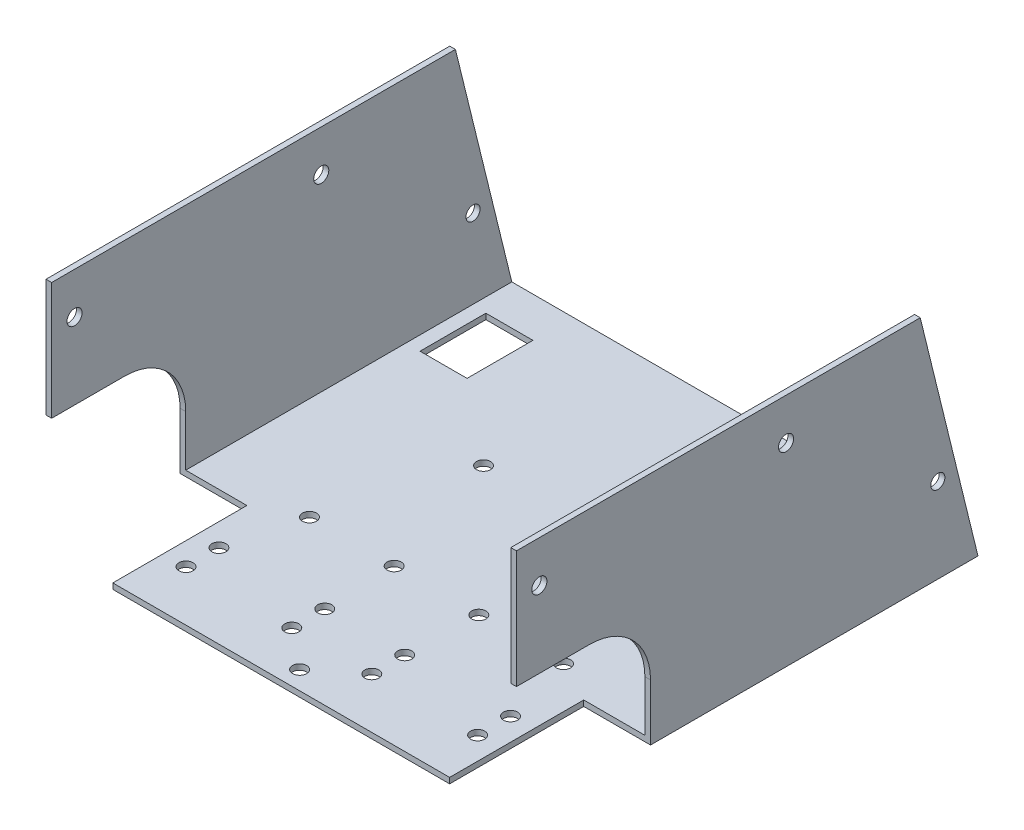
SolidWorks part; units mm, degrees
ref_plane "Alzado" through (0, 0, 0) normal (0, 0, 1) x (1, 0, 0)
ref_plane "Planta" through (0, 0, 0) normal (0, 1, 0) x (1, 0, 0)
ref_plane "Vista lateral" through (0, 0, 0) normal (1, 0, 0) x (0, 0, -1)
sketch "Croquis1" plane through (0, 0, 0) normal (0, 0, 1) x (1, 0, 0)
  line L0 (50, 0) -> (-50, 0)
  line L1 (-50, 0) -> (-50, 50)
  line L2 (-50, 50) -> (-48.8, 50)
  line L3 (-48.8, 50) -> (-48.8, 1.2)
  line L4 (-48.8, 1.2) -> (48.8, 1.2)
  line L5 (0, 1.2) -> (0, 0)
  line L6 (0, 0) -> (0, 13.9963) construction
  line L7 (48.8, 50) -> (48.8, 1.2)
  line L8 (50, 50) -> (48.8, 50)
  line L9 (50, 0) -> (50, 50)
  dimension "D1" = 50
  dimension "D2" = 50
  dimension "D3" = 1.2
  dimension "D4" = 1.2
extrude "Saliente-Extruir1" add sketch "Croquis1" against normal blind 100 contours L4 L7 L8 L9 L0 L1 L2 L3
sketch "Croquis2" plane through (0, 1.2, 0) normal (0, 1, 0) x (1, 0, 0)
  line L0 (0, 0) -> (0, 100) construction
  line L1 (-48.8, 0) -> (-35.8, 0)
  line L2 (-48.8, 0) -> (-48.8, 28.5)
  line L3 (-48.8, 28.5) -> (-35.8, 28.5)
  line L4 (-35.8, 0) -> (-35.8, 28.5)
  line L5 (-48.8, 100) -> (48.8, 100) construction
  line L6 (48.8, 28.5) -> (35.8, 28.5)
  line L7 (35.8, 0) -> (35.8, 28.5)
  line L8 (48.8, 0) -> (35.8, 0)
  line L9 (48.8, 0) -> (48.8, 28.5)
  dimension "D1" = 13
  dimension "D2" = 28.5
extrude "Cortar-Extruir2" cut sketch "Croquis2" against normal blind 10
ref_plane "Plano1" through (0, 1.2, 0) normal (0, 1, 0) x (1, 0, 0)
sketch "Croquis3" plane through (0, 1.2, 0) normal (0, 1, 0) x (1, 0, 0)
  line L0 (0, 0) -> (0, 100) construction
  line L1 (-48.8, 100) -> (48.8, 100) construction
  line L2 (-35.8, 0) -> (35.8, 0) construction
  circle A1 centre (0, 3.9) radius 1.5
  dimension "D1" = 3
  dimension "D2" = 3.9
extrude "Cortar-Extruir3" cut sketch "Croquis3" against normal blind 5
sketch "Croquis4" plane through (0, 1.2, 0) normal (0, 1, 0) x (1, 0, 0)
  line L0 (0, 0) -> (0, 100) construction
  line L1 (-48.8, 100) -> (48.8, 100) construction
  line L2 (0, 17.75) -> (-8.5, 17.75) construction
  line L3 (0, 10.75) -> (-8.5, 10.75) construction
  line L4 (-35.8, 14.25) -> (0, 14.25) construction
  line L5 (-8.5, 17.75) -> (-31, 17.75) construction
  line L6 (-35.8, 0) -> (-35.8, 28.5) construction
  circle A0 centre (-8.5, 17.75) radius 1.5
  circle A1 centre (-8.5, 10.75) radius 1.5
  circle A2 centre (8.5, 10.75) radius 1.5
  circle A3 centre (8.5, 17.75) radius 1.5
  circle A4 centre (-31, 17.75) radius 1.5
  circle A5 centre (-31, 10.75) radius 1.5
  circle A6 centre (31, 10.75) radius 1.5
  circle A7 centre (31, 17.75) radius 1.5
  dimension "D3" = 3
  dimension "D1" = 8.5
  dimension "D2" = 3.5
  dimension "D4" = 3.5
  dimension "D5" = 22.5
extrude "Cortar-Extruir4" cut sketch "Croquis4" against normal blind 10
sketch "Croquis5" plane through (0, 1.2, 0) normal (0, 1, 0) x (1, 0, 0)
  line L0 (-18, 100) -> (-18, 61) construction
  line L1 (-48.8, 100) -> (48.8, 100) construction
  line L2 (-48.8, 100) -> (-48.8, 0) construction
  line L3 (0, 100) -> (0, 0) construction
  line L4 (-35.8, 0) -> (35.8, 0) construction
  circle A0 centre (-18, 61) radius 1.5
  circle A1 centre (-27, 33) radius 1.5
  circle A2 centre (27, 33) radius 1.5
  circle A3 centre (18, 61) radius 1.5
  circle A4 centre (-9, 33) radius 1.5
  circle A5 centre (9, 33) radius 1.5
  dimension "D3" = 3
  dimension "D6" = 33
  dimension "D1" = 39
  dimension "D2" = 30.8
  dimension "D4" = 21.8
  dimension "D5" = 18
extrude "Cortar-Extruir6" cut sketch "Croquis5" against normal blind 10
sketch "Croquis6" plane through (-50, 0, 0) normal (-1, 0, 0) x (0, 0, 1)
  line L1 (0, 25) -> (0, 2.5)
  line L4 (-100, 0) -> (0, 0) construction
  line L6 (0, 2.5) -> (-28.5, 2.5)
  line L7 (0, 0) -> (0, 50) construction
  line L8 (-28.5, 2.5) -> (-28.5, 12)
  line L9 (-15.5, 25) -> (0, 25)
  arc A0 (-15.5, 25) -> (-28.5, 12) centre (-15.5, 12) ccw
  point P10 (-28.5, 25)
  dimension "D4" = 13
  dimension "D1" = 28.5
  dimension "D2" = 22.5
  dimension "D3" = 2.5
extrude "Cortar-Extruir8" cut sketch "Croquis6" against normal through all
sketch "Croquis7" plane through (0, 0, 0) normal (0, 0, 1) x (1, 0, 0)
  line L4 (-48.8, 2.5) -> (-50, 2.5)
  line L5 (-50, 2.5) -> (-50, 0)
  line L12 (50, 2.5) -> (48.8, 2.5)
  line L13 (48.8, 2.5) -> (48.8, 0)
  line L15 (48.8, 2.5) -> (48.8, 0)
  line L60 (-50, 2.5) -> (-50, 0)
  line L62 (50, 0) -> (50, 2.5)
  line L63 (50, 0) -> (50, 2.5)
  line L64 (-48.8, 0) -> (-48.8, 2.5)
  line L65 (-48.8, 0) -> (-48.8, 2.5)
  line L146 (-48.8, 2.5) -> (-50, 2.5)
  line L148 (50, 2.5) -> (48.8, 2.5)
  line L150 (-50, 0) -> (-48.8, 0)
  line L151 (-50, 0) -> (-48.8, 0)
  line L152 (48.8, 0) -> (50, 0)
  line L153 (48.8, 0) -> (50, 0)
  dimension "D1" = 0
  dimension "D2" = 0
extrude "Cortar-Extruir9" cut sketch "Croquis7" against normal blind 28.5
sketch "Croquis8" plane through (0, 1.2, 0) normal (0, 1, 0) x (1, 0, 0)
  line L0 (-40.8, 100) -> (-40.8, 28.5) construction
  line L1 (-48.8, 100) -> (48.8, 100) construction
  line L3 (40.8, 100) -> (40.8, 28.5) construction
  line L5 (-48.8, 100) -> (-48.8, 0) construction
  line L6 (48.8, 100) -> (48.8, 28.5) construction
  line L7 (0, 100) -> (0, 0) construction
  line L8 (-45.8, 89.3017) -> (-35.8, 89.3017)
  line L9 (-45.8, 89.3017) -> (-45.8, 75.3017)
  line L10 (-45.8, 75.3017) -> (-35.8, 75.3017)
  line L11 (-35.8, 89.3017) -> (-35.8, 75.3017)
  line L12 (-45.8, 89.3017) -> (-35.8, 75.3017) construction
  line L13 (-45.8, 75.3017) -> (-35.8, 89.3017) construction
  line L14 (45.8, 75.3017) -> (35.8, 75.3017)
  line L15 (35.8, 89.3017) -> (35.8, 75.3017)
  line L16 (45.8, 89.3017) -> (35.8, 89.3017)
  line L17 (45.8, 89.3017) -> (45.8, 75.3017)
  point P12 (-40.8, 82.3017)
  dimension "D1" = 8
  dimension "D2" = 8
  dimension "D3" = 14
  dimension "D4" = 10
extrude "Cortar-Extruir10" cut sketch "Croquis8" against normal blind 10
sketch "Croquis9" plane through (-50, 0, 0) normal (-1, 0, 0) x (0, 0, 1)
  line L0 (-100, 0) -> (-100, -2.8) construction
  line L1 (-100, -2.8) -> (-98.9305, -3.3442)
  line L3 (-98.9305, -3.3442) -> (-85.8279, 50)
  line L4 (-100, 50) -> (0, 50) construction
  line L5 (-100, -2.8) -> (-87.0311, 50) construction
  line L6 (-100, -2.8) -> (-100, 50)
  line L7 (-100, 50) -> (-85.8279, 50)
  dimension "D1" = 2.8
  dimension "D2" = 1.2
  dimension "D3" = 13.8
extrude "Cortar-Extruir11" cut sketch "Croquis9" against normal through all
sketch "Croquis10" plane through (-50, 0, 0) normal (-1, 0, 0) x (0, 0, 1)
  line L0 (-89.569, 0) -> (-89.569, 18) construction
  line L1 (-98.1091, 0) -> (-28.5, 0) construction
  line L2 (-98.1091, 0) -> (-85.8279, 50) construction
  circle A0 centre (-89.569, 18) radius 1.5
  dimension "D1" = 3
  dimension "D2" = 18
  dimension "D3" = 4
extrude "Cortar-Extruir12" cut sketch "Croquis10" against normal through all
sketch "Croquis11" plane through (-50, 0, 0) normal (-1, 0, 0) x (0, 0, 1)
  line L0 (-98.1091, 0) -> (-57.3091, 0) construction
  line L1 (-98.1091, 0) -> (-28.5, 0) construction
  line L2 (-57.3091, 0) -> (-57.3091, 41.2) construction
  circle A0 centre (-57.3091, 41.2) radius 1.6
  circle A1 centre (-4.8688, 41.2) radius 1.6
  point P9 (0, 0)
  point P10 (-68.1007, 40.5)
  point P11 (-3.6688, 40.5)
  dimension "D3" = 3.2
  dimension "D1" = 40.8
  dimension "D2" = 41.2
extrude "Cortar-Extruir13" cut sketch "Croquis11" against normal through all
